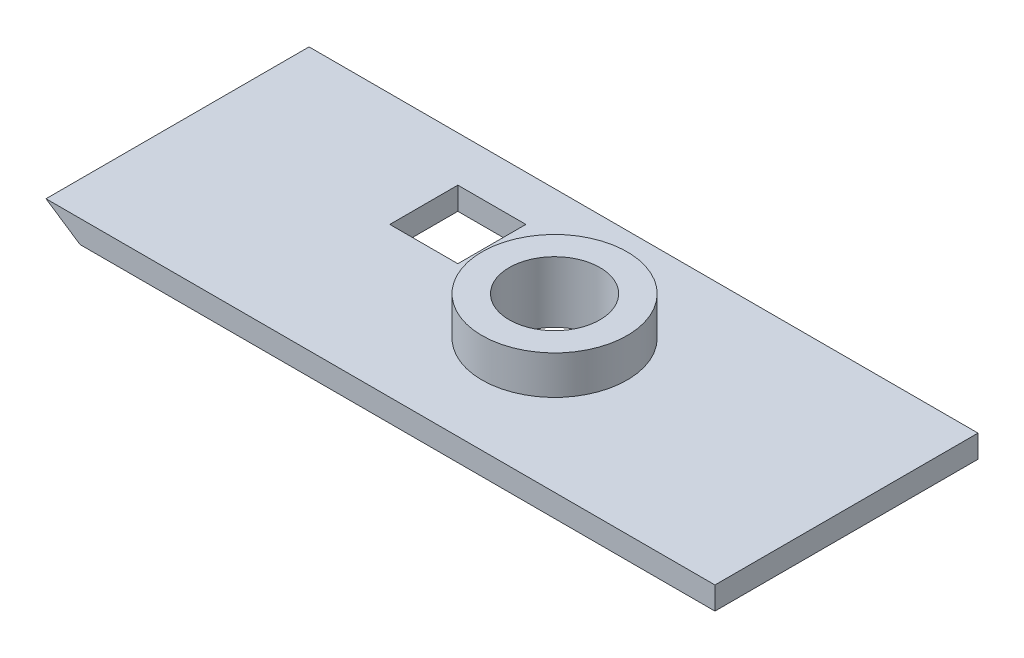
SolidWorks part; units mm, degrees
ref_plane "前视基准面" through (0, 0, 0) normal (0, 0, 1) x (1, 0, 0)
ref_plane "上视基准面" through (0, 0, 0) normal (0, 1, 0) x (1, 0, 0)
ref_plane "右视基准面" through (0, 0, 0) normal (1, 0, 0) x (0, 0, -1)
sketch "草图2" plane through (0, 0, 0) normal (0, 1, 0) x (1, 0, 0)
  line L1 (-30.1985, 7.2699) -> (-0.1985, 7.2699)
  line L2 (-30.1985, 7.2699) -> (-30.1985, -4.3301)
  line L3 (-30.1985, -4.3301) -> (-0.1985, -4.3301)
  line L4 (-0.1985, 7.2699) -> (-0.1985, -4.3301)
  line L5 (-32.1582, -4.3301) -> (-32.1582, 7.2699) construction
  line L7 (-0.1985, 1.4699) -> (-30.1985, 1.4699) construction
  line L9 (-34.0753, 7.2699) -> (0.3265, 7.2699) construction
  circle A1 centre (-15.1582, 1.5574) radius 2
  circle A2 centre (-15.1582, 1.5574) radius 3.2 construction
  circle A3 centre (-15.1582, 1.5574) radius 3.2 construction
  dimension "D4" = 4
  dimension "D5" = 6.4
  dimension "D1" = 30
extrude "凸台-拉伸1" add sketch "草图2" along normal blind 1
sketch "草图3" plane through (0, 1, 0) normal (0, 1, 0) x (1, 0, 0)
  circle A0 centre (-15.1582, 1.5574) radius 2
  circle A1 centre (-15.1582, 1.5574) radius 3.2
extrude "凸台-拉伸2" add sketch "草图3" along normal blind 1.7
sketch "草图4" plane through (0, 0, 0) normal (0, -1, 0) x (1, 0, 0)
  line L5 (-31.6367, 4.3301) -> (-31.6367, -7.2699) construction
  line L7 (-23.1367, -2.2699) -> (-20.1367, -2.2699)
  line L8 (-23.1367, -2.2699) -> (-23.1367, -5.2699)
  line L9 (-23.1367, -5.2699) -> (-20.1367, -5.2699)
  line L10 (-20.1367, -2.2699) -> (-20.1367, -5.2699)
  line L11 (-0.1985, -7.2699) -> (-30.1985, -7.2699) construction
  point P10 (-21.4, -0.2699)
  dimension "D1" = 3
  dimension "D3" = 5
  dimension "D2" = 8.5
extrude "切除-拉伸1" cut sketch "草图4" against normal blind 5
sketch "草图5" plane through (0, 0, -7.2699) normal (0, 0, -1) x (-1, 0, 0)
  line L0 (30.1985, 1) -> (30.1985, 0)
  line L1 (30.1985, 0) -> (31.6985, 1)
  line L2 (31.6985, 1) -> (30.1985, 1)
  line L3 (32.1582, 1) -> (21.6582, 1) construction
  point P4 (31.1985, 1)
  dimension "D1" = 1.5
extrude "凸台-拉伸3" add sketch "草图5" against normal up to surface (11.6 mm away) up to face at (-15.1985, 0.5, 4.3301)
sketch "草图6" plane through (0, 0, 0) normal (0, -1, 0) x (1, 0, 0)
  line L0 (-0.1985, -7.2699) -> (-30.1985, -7.2699) construction
  line L1 (-0.1985, 4.3301) -> (-2.1985, 4.3301)
  line L2 (-0.1985, 4.3301) -> (-0.1985, -7.2699)
  line L3 (-0.1985, -7.2699) -> (-2.1985, -7.2699)
  line L4 (-2.1985, 4.3301) -> (-2.1985, -7.2699)
  dimension "D1" = 2
extrude "切除-拉伸2" cut sketch "草图6" against normal blind 1
sketch "草图7" plane through (0, 0, -7.2699) normal (0, 0, -1) x (-1, 0, 0)
  line L0 (31.6985, 1) -> (30.1985, 0)
  line L1 (30.1985, 0) -> (29.3151, 0)
  line L2 (2.1985, 0) -> (30.1985, 0) construction
  line L3 (29.3151, 0) -> (30.8151, 1)
  line L4 (2.1985, 1) -> (31.6985, 1) construction
  line L5 (30.8151, 1) -> (31.6985, 1)
  dimension "D1" = 0.49
